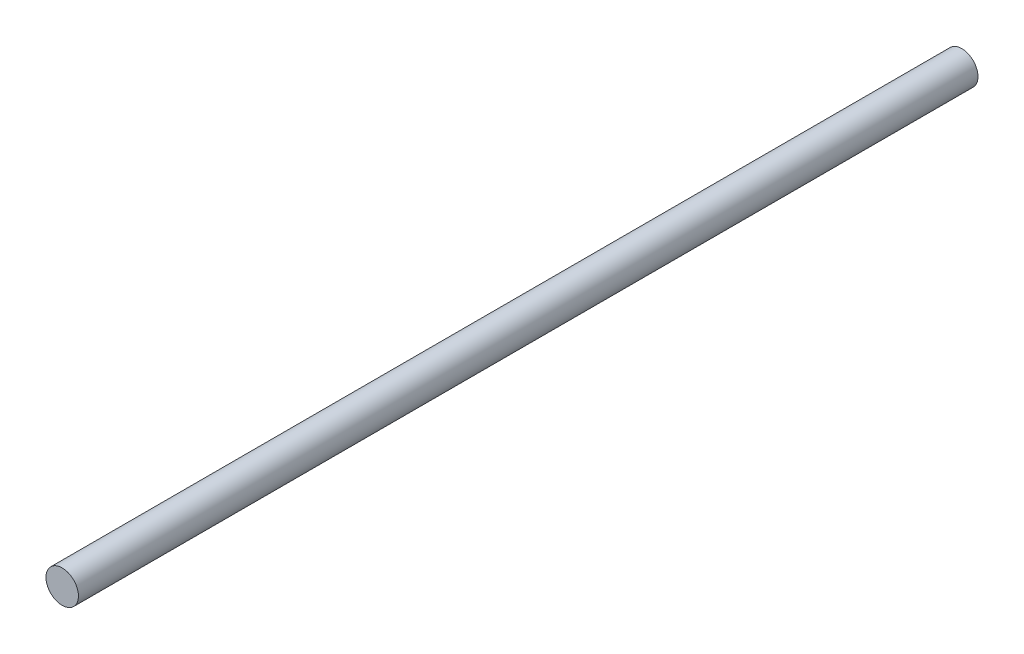
SolidWorks part; units mm, degrees
material "Plain Carbon Steel"
ref_plane "Front Plane" through (0, 0, 0) normal (0, 0, 1) x (1, 0, 0)
ref_plane "Top Plane" through (0, 0, 0) normal (0, 1, 0) x (1, 0, 0)
ref_plane "Right Plane" through (0, 0, 0) normal (1, 0, 0) x (0, 0, -1)
sketch "Sketch1" plane through (0, 0, 0) normal (0, 0, 1) x (1, 0, 0)
  line L0 (2.75, 0) -> (-2.75, 0) construction
  circle A0 centre (0, 0) radius 3.25
  dimension "D1" = 6.5
extrude "Boss-Extrude1" add sketch "Sketch1" along normal blind 180
